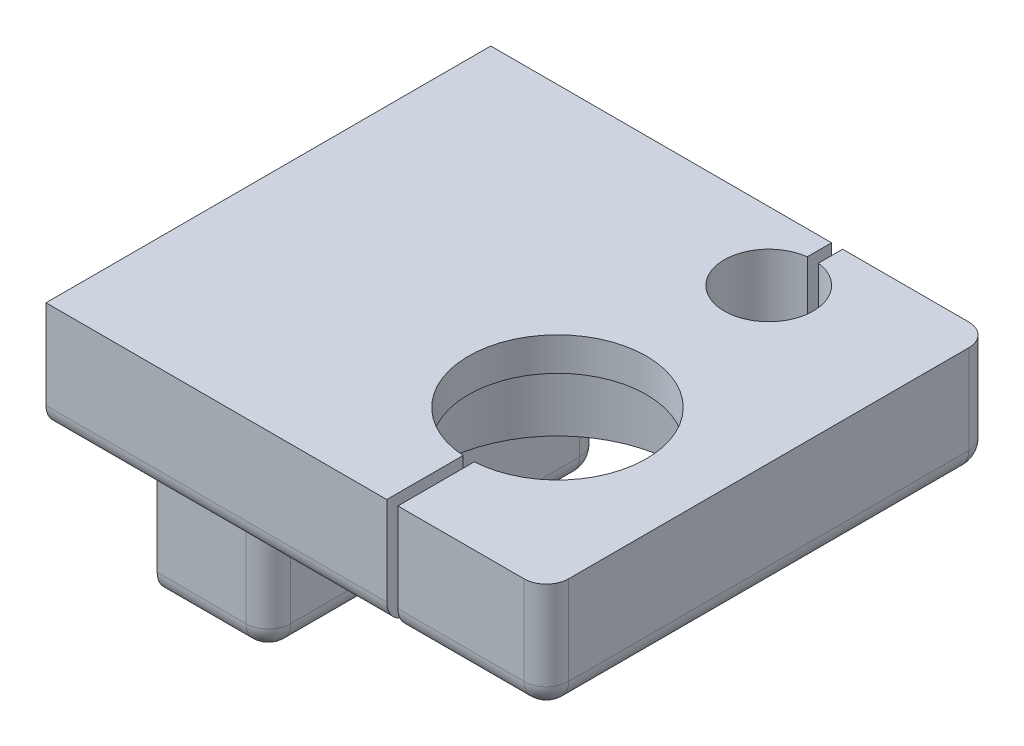
SolidWorks part; units mm, degrees
ref_plane "Front Plane" through (0, 0, 0) normal (0, 0, 1) x (1, 0, 0)
ref_plane "Top Plane" through (0, 0, 0) normal (0, 1, 0) x (1, 0, 0)
ref_plane "Right Plane" through (0, 0, 0) normal (1, 0, 0) x (0, 0, -1)
sketch "Sketch2" plane through (0, 0, 0) normal (0, 1, 0) x (1, 0, 0)
  line L0 (31.15, -6.15) -> (31.15, -25.15) construction
  line L1 (0, 0) -> (45, 0)
  line L2 (0, 0) -> (0, -40)
  line L3 (0, -40) -> (45, -40)
  line L4 (45, 0) -> (45, -40)
  line L5 (31.15, -2.1814) -> (31.15, -6.15) construction
  line L6 (30.65, 0) -> (31.65, 0)
  line L7 (30.65, 0) -> (30.65, -2.1814)
  line L8 (30.65, -2.1814) -> (31.65, -2.1814)
  line L9 (31.65, 0) -> (31.65, -2.1814)
  line L10 (31.15, -25.15) -> (31.15, -33.1344) construction
  line L12 (30.65, -40) -> (31.65, -40)
  line L13 (30.65, -40) -> (30.65, -33.1344)
  line L14 (30.65, -33.1344) -> (31.65, -33.1344)
  line L15 (31.65, -40) -> (31.65, -33.1344)
  circle A2 centre (31.15, -6.15) radius 4
  circle A3 centre (31.15, -25.15) radius 11 construction
  circle A4 centre (31.15, -25.15) radius 8
  dimension "D3" = 13.85
  dimension "D4" = 6.15
  dimension "D5" = 19
  dimension "D6" = 45
  dimension "D7" = 40
  dimension "D8" = 1
  dimension "D1" = 22
  dimension "D2" = 8
  dimension "D9" = 3
  dimension "D10" = 1
extrude "Boss-Extrude1" add sketch "Sketch2" along normal blind 10 contours L4 L1 L2 L3 A2 region at (21.0374, 0, 19.7324)
sketch "Sketch3" plane through (0, 0, 0) normal (0, -1, 0) x (1, 0, 0)
  circle A0 centre (31.15, 25.15) radius 11 construction
  circle A1 centre (31.15, 25.15) radius 11
  circle A2 centre (31.15, 25.15) radius 7
  dimension "D1" = 4
extrude "Cut-Extrude1" cut sketch "Sketch3" against normal blind 7
sketch "Sketch6" plane through (0, 0, 0) normal (0, 0, -1) x (-1, 0, 0)
  line L1 (0, 0) -> (-10, 0)
  line L2 (0, 0) -> (0, -18)
  line L3 (0, -18) -> (-10, -18)
  line L4 (-10, 0) -> (-10, -18)
  dimension "D1" = 18
  dimension "D2" = 10
extrude "Boss-Extrude4" add sketch "Sketch6" against normal blind 30
sketch "Sketch7" plane through (10, 0, 0) normal (1, 0, 0) x (0, 0, -1)
  line L0 (-21, -3.8038) -> (-15, -14.1962) construction
  line L1 (-15, -14.1962) -> (-9, -3.8038) construction
  line L2 (-9, -3.8038) -> (-21, -3.8038) construction
  line L4 (-15, -14.1962) -> (-15, -18) construction
  line L7 (-30, -18) -> (0, -18) construction
  line L8 (-15, -3.8038) -> (-15, 0) construction
  line L9 (-30, 0) -> (0, 0) construction
  circle A0 centre (-9, -3.8038) radius 1.8
  circle A1 centre (-15, -14.1962) radius 1.8
  circle A2 centre (-21, -3.8038) radius 1.8
  dimension "D1" = 3.6
  dimension "D2" = 12
extrude "Cut-Extrude2" cut sketch "Sketch7" against normal through all
sketch "Sketch8" plane through (10, 0, 0) normal (1, 0, 0) x (0, 0, -1)
  circle A0 centre (-21, -3.8038) radius 3
  circle A1 centre (-15, -14.1962) radius 3
  circle A2 centre (-9, -3.8038) radius 3
  dimension "D1" = 6
extrude "Cut-Extrude3" cut sketch "Sketch8" against normal blind 5
fillet "Fillet1" radius 2 12 edges at (10, -9, 30) (15.325, 0, 40) (38.325, 0, 40) (45, 5, 40) (45, 0, 20) (38.325, 0, 0) (10, -9, 0) (20.325, 0, 0) (45, 5, 0) (5, -18, 30) (5, -18, 0) (10, -18, 15)
